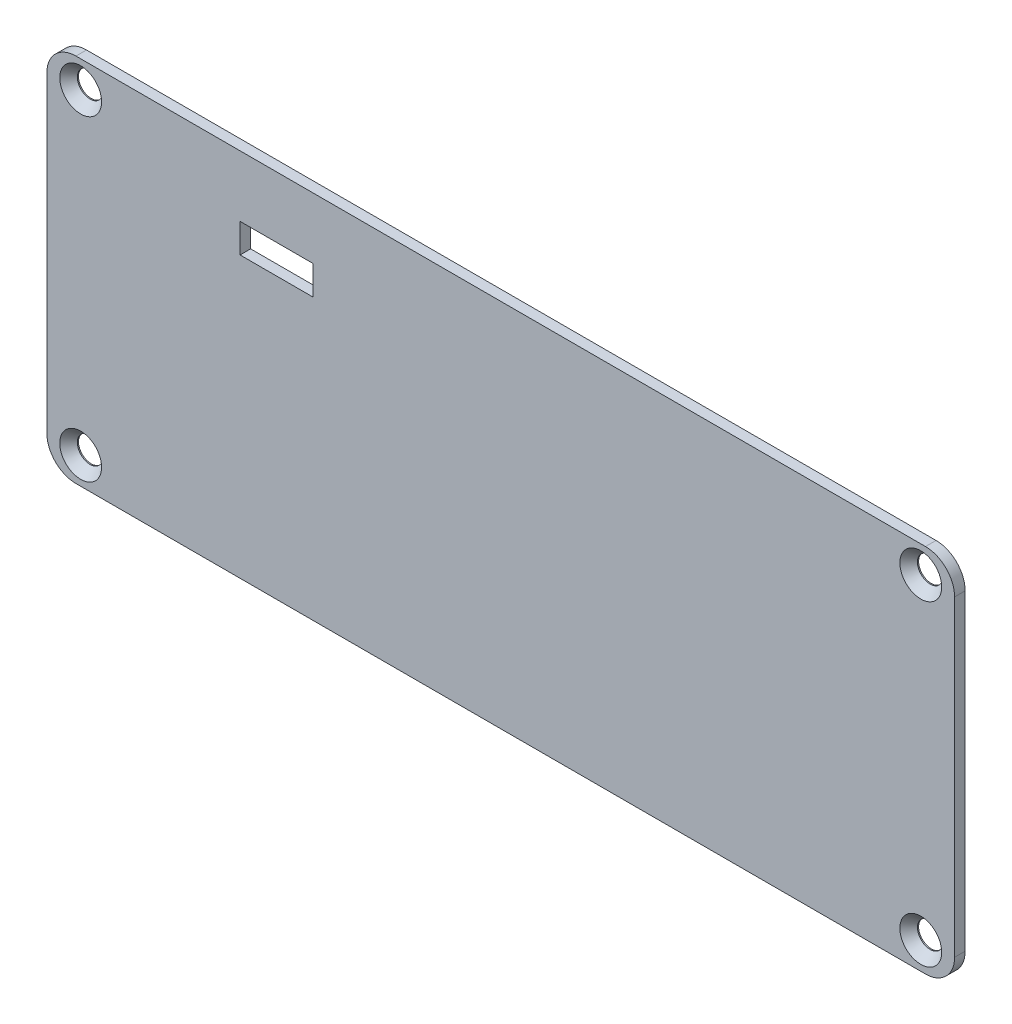
SolidWorks part; units mm, degrees
other "Markup1"
sketch "Sketch3" plane through (0, 0, 0) normal (-0.9973, 0.0561, -0.0476) x (-0.0483, -0.0106, 0.9988)
ref_plane "Front Plane" through (0, 0, 0) normal (0, 0, 1) x (1, 0, 0)
ref_plane "Top Plane" through (0, 0, 0) normal (0, 1, 0) x (1, 0, 0)
ref_plane "Right Plane" through (0, 0, 0) normal (1, 0, 0) x (0, 0, -1)
sketch "Sketch1" plane through (0, 0, 0) normal (0, 0, 1) x (1, 0, 0)
  line L1 (0, 0) -> (124.8, 0)
  line L2 (0, 0) -> (0, -50.9)
  line L3 (0, -50.9) -> (124.8, -50.9)
  line L4 (124.8, 0) -> (124.8, -50.9)
  line L17 (26.565, -8.4) -> (36.565, -8.4)
  line L18 (26.565, -8.4) -> (26.565, -12.4)
  line L19 (26.565, -12.4) -> (36.565, -12.4)
  line L20 (36.565, -8.4) -> (36.565, -12.4)
  point P5 (31.565, -10.4)
  point P7 (31.565, -8.4)
  point P8 (36.565, -10.4)
  dimension "D1" = 124.8
  dimension "D2" = 50.9
  dimension "D3" = 31.565
  dimension "D4" = 10.4
  dimension "D5" = 31.565
  dimension "D6" = 10.4
  dimension "D7" = 10
  dimension "D8" = 4
extrude "Boss-Extrude1" add sketch "Sketch1" along normal blind 1.45 contours L4 L1 L2 L3 region at (62.5954, -25.5454, 0)
hole_wizard "CSK for M3.5 Flat Head Machine Screw1" positions "3DSketch1" profile "Sketch2" countersink size "M3.5" standard "ANSI Metric" end condition through all
sketch3d "3DSketch1"
  line L3 (0, 0, 1.45) -> (124.8, 0, 1.45) construction
  line L4 (124.8, 0, 1.45) -> (124.8, -50.9, 1.45) construction
  point P0 (4.65, -3.7, 1.45)
  point P2 (120.15, -3.7, 1.45)
  point P4 (120.15, -47.2, 1.45)
  point P6 (4.65, -47.2, 1.45)
  dimension "D1" = 115.5
  dimension "D2" = 43.5
  dimension "D3" = 3.7
  dimension "D4" = 4.65
sketch "Sketch2" plane through (4.65, -3.7, 1.45) normal (1, 0, 0) x (0, -1, 0)
  line L0 (0, 0) -> (0, 1.45)
  line L1 (0, 1.45) -> (1.75, 1.45)
  line L2 (1.75, 1.45) -> (1.75, 1.2942)
  line L3 (1.75, 1.2942) -> (2.875, 0)
  line L5 (2.875, 0) -> (0, 0)
  line L6 (-1.75, 1.2942) -> (-2.875, 0) construction
  line L11 (0, -6.35) -> (0, 107.95) construction
  dimension "Thru Hole Dia." = 3.5
  dimension "Thru Hole Depth" = 1.45
  dimension "Near C'Sink Dia." = 5.75
  dimension "Near C'Sink Angle" = 82
fillet "Fillet2" radius 4 4 edges at (0, 0, 0.725) (124.8, 0, 0.725) (124.8, -50.9, 0.725) (0, -50.9, 0.725)
